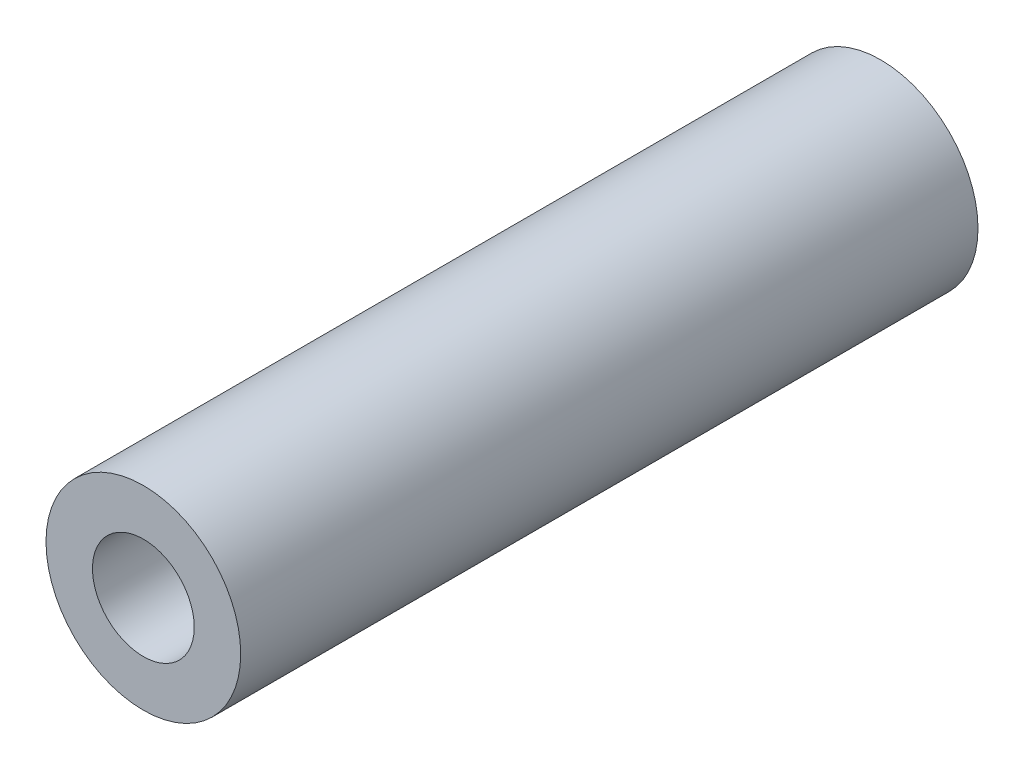
SolidWorks part; units mm, degrees
ref_plane "Front Plane" through (0, 0, 0) normal (0, 0, 1) x (1, 0, 0)
ref_plane "Top Plane" through (0, 0, 0) normal (0, 1, 0) x (1, 0, 0)
ref_plane "Right Plane" through (0, 0, 0) normal (1, 0, 0) x (0, 0, -1)
sketch "Sketch1" plane through (0, 0, 0) normal (0, 0, 1) x (1, 0, 0)
  circle A0 centre (0, 0) radius 2.4892
  circle A1 centre (0, 0) radius 4.7625
  dimension "D1" = 4.9784
  dimension "D2" = 9.525
extrude "Boss-Extrude1" add sketch "Sketch1" along normal mid plane 36.068 contours A0 | A1 region at (0, 0, 0)
